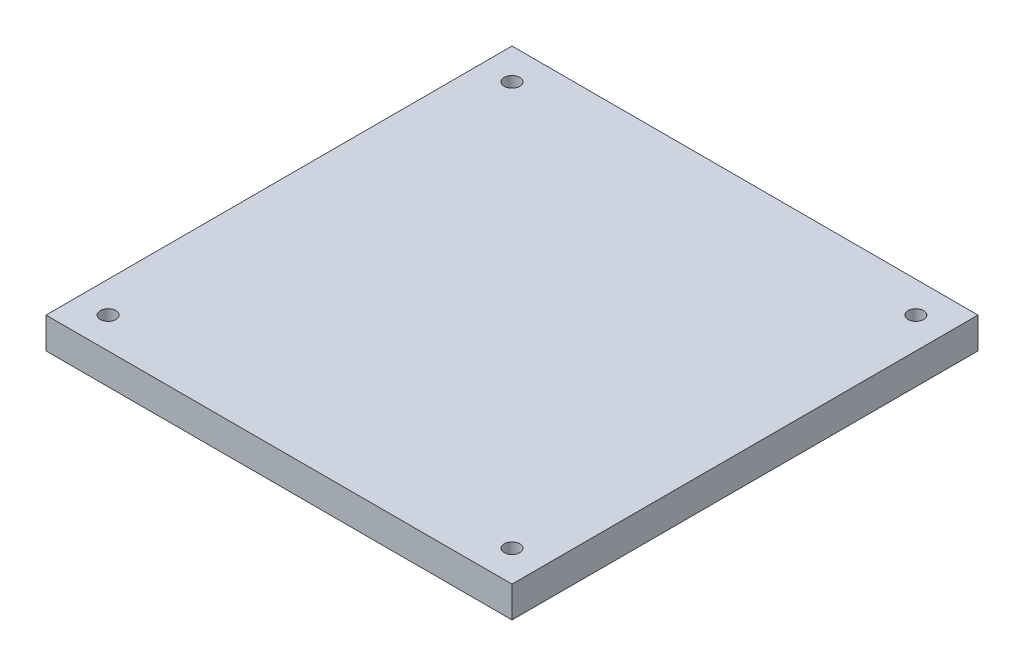
SolidWorks part; units mm, degrees
material "6061 Alloy"
ref_plane "Plano frontal" through (0, 0, 0) normal (0, 0, 1) x (1, 0, 0)
ref_plane "Plano superior" through (0, 0, 0) normal (0, 1, 0) x (1, 0, 0)
ref_plane "Plano direito" through (0, 0, 0) normal (1, 0, 0) x (0, 0, -1)
sketch "Sketch1" plane through (0, 0, 0) normal (0, 1, 0) x (1, 0, 0)
  line L1 (-75, 75) -> (75, 75)
  line L2 (-75, 75) -> (-75, -75)
  line L3 (-75, -75) -> (75, -75)
  line L4 (75, 75) -> (75, -75)
  line L5 (-75, 75) -> (75, -75) construction
  line L6 (-75, -75) -> (75, 75) construction
  point P0 (0, 0)
  dimension "D1" = 150
extrude "Boss-Extrude1" add sketch "Sketch1" along normal blind 10
hole_wizard "M6 Tapped Hole1" positions "3DSketch1" profile "Sketch4" tap size "M6" standard "DIN" end condition through all
sketch3d "3DSketch1"
  line L0 (-75, 0, 75) -> (75, 0, 75) construction
  line L1 (-75, 0, -75) -> (-75, 0, 75) construction
  line L2 (75, 0, 75) -> (75, 0, -75) construction
  line L3 (75, 0, -75) -> (-75, 0, -75) construction
  point P0 (65, 0, 65)
  point P2 (65, 0, -65)
  point P4 (-65, 0, -65)
  point P6 (-65, 0, 65)
  dimension "D1" = 10
  dimension "D2" = 10
  dimension "D5" = 10
  dimension "D6" = 10
cosmetic thread "Hole Thread1"
cosmetic thread "Hole Thread2"
cosmetic thread "Hole Thread3"
cosmetic thread "Hole Thread4"
sketch "Sketch4" plane through (65, 0, 65) normal (1, 0, 0) x (0, 0, -1)
  line L0 (0, 0) -> (0, 10)
  line L1 (0, 10) -> (2.5, 10)
  line L2 (2.5, 10) -> (2.5, 0)
  line L5 (2.5, 0) -> (0, 0)
  line L11 (0, -6.35) -> (0, 107.95) construction
  dimension "Thru Tap Drill Dia." = 5
  dimension "Thru Tap Drill Depth" = 10
